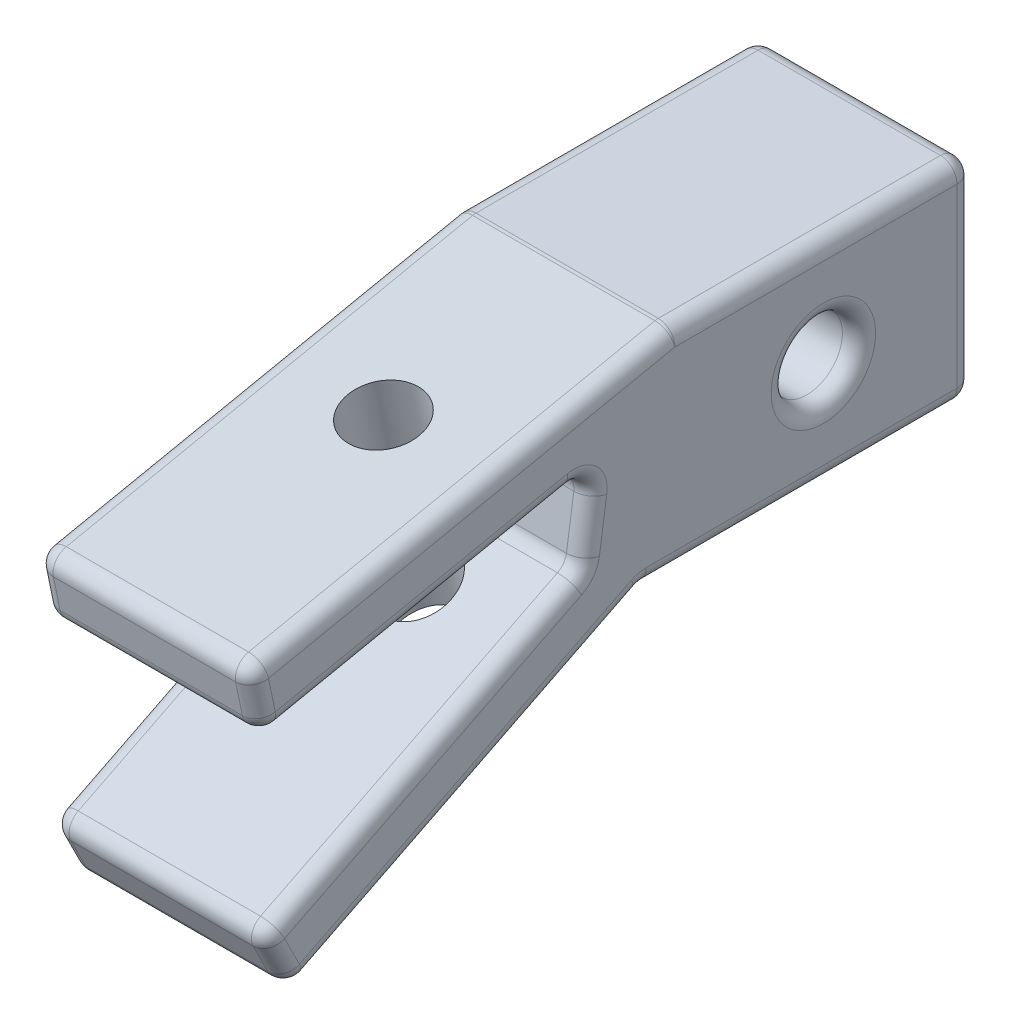
SolidWorks part; units mm, degrees
ref_plane "Front Plane" through (0, 0, 0) normal (0, 0, 1) x (1, 0, 0)
ref_plane "Top Plane" through (0, 0, 0) normal (0, 1, 0) x (1, 0, 0)
ref_plane "Right Plane" through (0, 0, 0) normal (1, 0, 0) x (0, 0, -1)
sketch "Sketch1" plane through (0, 0, 0) normal (1, 0, 0) x (0, 0, -1)
  line L0 (30.8927, -23.4242) -> (10.8927, -23.4242) construction
  line L1 (10.8927, -23.4242) -> (10.8927, -40.7747) construction
  line L2 (10.0854, -23.6277) -> (35.6805, -18.3536)
  line L3 (10.0854, -23.6277) -> (10.8927, -27.5454)
  line L4 (10.8927, -27.5454) -> (30.8927, -23.4242)
  line L8 (30.8927, -23.4242) -> (30.166, -28.3711)
  line L9 (30.166, -28.3711) -> (10.8927, -38.0407)
  line L10 (33.8209, -31.0126) -> (12.6864, -41.616)
  line L12 (35.6805, -18.3536) -> (53.8055, -18.3536)
  line L15 (53.8055, -18.3536) -> (53.8055, -31.0126)
  line L17 (10.8927, -38.0407) -> (12.6864, -41.616)
  line L18 (35.6805, -18.3536) -> (33.8209, -31.0126) construction
  line L19 (33.8209, -31.0126) -> (53.8055, -31.0126)
  line L20 (44.743, -18.3536) -> (44.743, -31.0126) construction
  line L21 (53.8055, -24.6831) -> (30.7078, -24.6831) construction
  circle A1 centre (44.743, -24.6831) radius 2.15
  dimension "D2" = 4.3
  dimension "D1" = 4
  dimension "D3" = 4.9469
  dimension "D4" = 20
extrude "Boss-Extrude1" add sketch "Sketch1" along normal blind 13 contours L2 L12 L15 L19 L10 L17 L9 L8 L4 L3 | A1
fillet "Fillet1" radius 1 32 edges at (6.5, -23.4242, -30.8927) (6.5, -28.3711, -30.166) (6.5, -27.5454, -10.8927) (6.5, -23.6277, -10.0854) (6.5, -18.3536, -35.6805) (6.5, -18.3536, -53.8055) (6.5, -31.0126, -53.8055) (6.5, -31.0126, -33.8209) (6.5, -38.0407, -10.8927) (6.5, -41.616, -12.6864) (0, -24.6831, -46.893) (0, -25.4848, -20.8927) (0, -25.8977, -30.5294) (0, -33.2059, -20.5294) (0, -39.8284, -11.7896) (0, -36.3143, -23.2537) (0, -31.0126, -43.8132) (0, -24.6831, -53.8055) (0, -18.3536, -44.743) (0, -20.9906, -22.8829) (0, -25.5865, -10.489) (13, -24.6831, -46.893) (13, -20.9906, -22.8829) (13, -18.3536, -44.743) (13, -24.6831, -53.8055) (13, -31.0126, -43.8132) (13, -36.3143, -23.2537) (13, -39.8284, -11.7896) (13, -33.2059, -20.5294) (13, -25.8977, -30.5294) (13, -25.4848, -20.8927) (13, -25.5865, -10.489)
sketch "Sketch2" plane through (13, 0, 0) normal (1, 0, 0) x (0, 0, -1)
  line L0 (30.2417, -27.8561) -> (26.1917, -27.8561) construction
  dimension "D1" = 4.05
sketch "Sketch3" plane through (0, -24.6589, -5.0812) normal (0, 0.9794, 0.2018) x (1, 0, 0)
  line L0 (13, 20.0308) -> (0, 20.0308) construction
  line L1 (13, 23.9975) -> (13, 20.0308) construction
  line L2 (0, 6.1094) -> (0, 31.1402) construction
  circle A0 centre (6.5, 20.0308) radius 2.15
  dimension "D1" = 4.3
extrude "Cut-Extrude1" cut sketch "Sketch3" against normal blind 23
